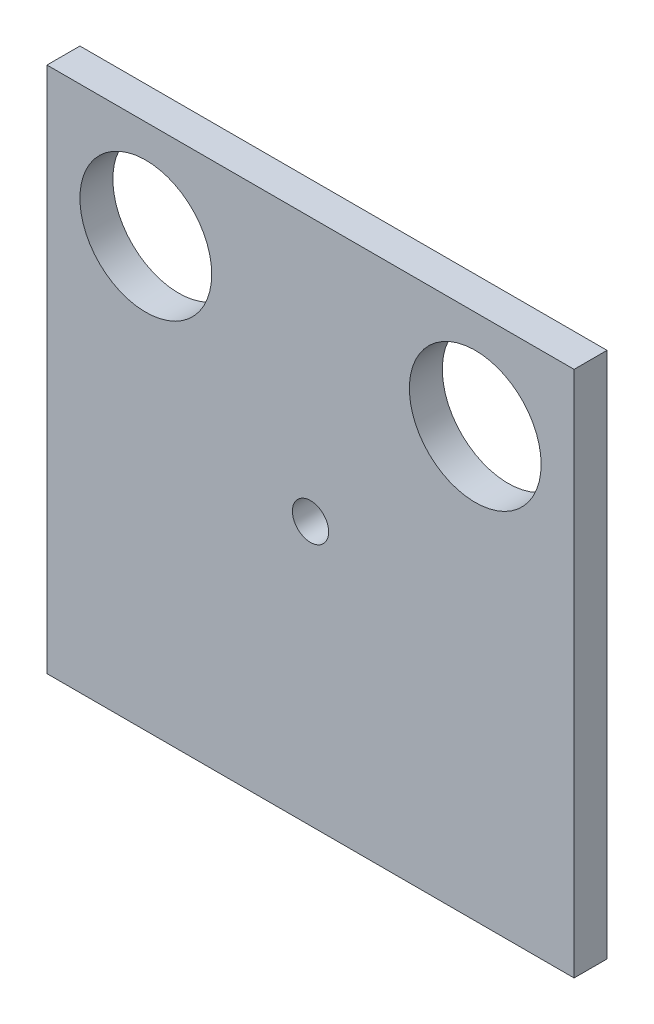
SolidWorks part; units mm, degrees
material "6061 Alloy"
ref_plane "Front Plane" through (0, 0, 0) normal (0, 0, 1) x (1, 0, 0)
ref_plane "Top Plane" through (0, 0, 0) normal (0, 1, 0) x (1, 0, 0)
ref_plane "Right Plane" through (0, 0, 0) normal (1, 0, 0) x (0, 0, -1)
other "Center of Mass"
sketch "Sketch1" plane through (0, 0, 0) normal (0, 0, 1) x (1, 0, 0)
  line L0 (19.05, 82.55) -> (82.55, 82.55) construction
  line L1 (0, 0) -> (101.6, 0)
  line L2 (0, 0) -> (0, 101.6)
  line L3 (0, 101.6) -> (101.6, 101.6)
  line L4 (101.6, 0) -> (101.6, 101.6)
  line L5 (50.8, 101.6) -> (50.8, 82.55) construction
  line L6 (0, 101.6) -> (101.6, 0) construction
  circle A0 centre (19.05, 82.55) radius 12.7
  circle A1 centre (82.55, 82.55) radius 12.7
  circle A2 centre (50.8, 50.8) radius 3.4925
  dimension "D4" = 25.4
  dimension "D5" = 6.985
  dimension "D1" = 101.6
  dimension "D2" = 19.05
  dimension "D3" = 63.5
extrude "Boss-Extrude1" add sketch "Sketch1" along normal blind 6.35
ref_plane "Plane1" through (50.8, 0, 0) normal (1, 0, 0) x (0, 0, -1)
